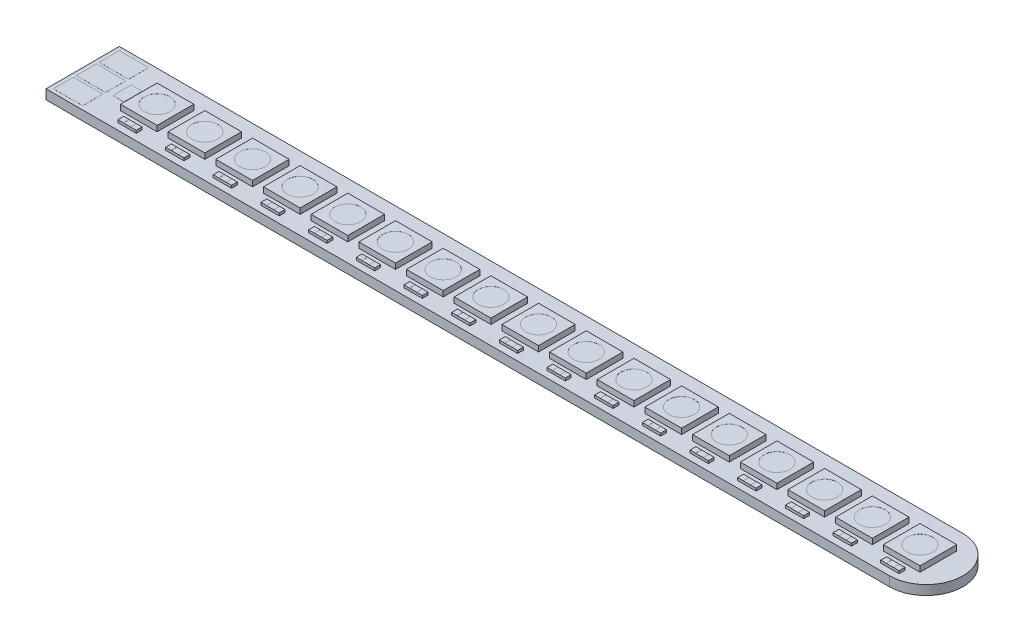
SolidWorks part; units mm, degrees
ref_plane "Front Plane" through (0, 0, 0) normal (0, 0, 1) x (1, 0, 0)
ref_plane "Top Plane" through (0, 0, 0) normal (0, 1, 0) x (1, 0, 0)
ref_plane "Right Plane" through (0, 0, 0) normal (1, 0, 0) x (0, 0, -1)
sketch "Sketch2" plane through (0, 0, 0) normal (0, 1, 0) x (1, 0, 0)
  line L0 (60, 0) -> (-60, 0) construction
  line L3 (55, 5) -> (-60, 5)
  line L4 (-60, 5) -> (-60, -5)
  line L5 (-60, -5) -> (55, -5)
  line L6 (-57.5, 1.75) -> (-57.5, -1.75) construction
  line L7 (-59.5, 4.5) -> (-55.5, 4.5)
  line L8 (-59.5, 4.5) -> (-59.5, 1.75)
  line L9 (-59.5, 1.75) -> (-55.5, 1.75)
  line L10 (-55.5, 4.5) -> (-55.5, 1.75)
  line L11 (-59.5, 1.375) -> (-55.5, 1.375)
  line L12 (-59.5, 1.375) -> (-59.5, -1.375)
  line L13 (-59.5, -1.375) -> (-55.5, -1.375)
  line L14 (-55.5, 1.375) -> (-55.5, -1.375)
  line L15 (-59.5, -1.75) -> (-55.5, -1.75)
  line L16 (-59.5, -1.75) -> (-59.5, -4.5)
  line L17 (-59.5, -4.5) -> (-55.5, -4.5)
  line L18 (-55.5, -1.75) -> (-55.5, -4.5)
  line L19 (-50.35, -3.3) -> (-50.35, -4.1)
  line L20 (-54.64, 1.25) -> (-53.14, 1.25)
  line L21 (-54.64, 1.25) -> (-54.64, -1.25)
  line L22 (-54.64, -1.25) -> (-53.14, -1.25)
  line L23 (-53.14, 1.25) -> (-53.14, -1.25)
  line L24 (-52.35, 2.5) -> (-47.35, 2.5)
  line L25 (-52.35, 2.5) -> (-52.35, -2.5)
  line L26 (-52.35, -2.5) -> (-47.35, -2.5)
  line L27 (-47.35, 2.5) -> (-47.35, -2.5)
  line L28 (-51.1, -3.3) -> (-48.6, -3.3)
  line L29 (-51.1, -3.3) -> (-51.1, -4.1)
  line L30 (-51.1, -4.1) -> (-48.6, -4.1)
  line L31 (-48.6, -3.3) -> (-48.6, -4.1)
  line L32 (-50.35, -4.1) -> (-49.35, -4.1)
  line L33 (-49.35, -4.1) -> (-49.35, -3.3)
  line L34 (-50.35, -3.7) -> (-49.35, -3.7) construction
  arc A2 (55, -5) -> (55, 5) centre (55, 0) ccw
  circle A3 centre (-49.85, 0) radius 1.75
  point P1 (60, 0)
  point P6 (60, 0)
  point P7 (-55.5, 0)
  point P21 (-57.5, 0)
  point P22 (-53.14, 0)
  point P28 (-59.5, 0)
  point P34 (-49.85, 2.5)
  point P35 (-52.35, 0)
  point P37 (-49.85, -3.3)
  point P51 (-49.85, -3.7)
  dimension "D11" = 3.5
  dimension "D1" = 120
  dimension "D2" = 10
  dimension "D3" = 2.75
  dimension "D4" = 0.5
  dimension "D5" = 0.5
  dimension "D6" = 4
  dimension "D7" = 5.36
  dimension "D8" = 2.5
  dimension "D9" = 1.5
  dimension "D10" = 5
  dimension "D12" = 7.65
  dimension "D13" = 0.9
  dimension "D14" = 2.5
  dimension "D15" = 0.8
  dimension "D16" = 1
extrude "PCB" add sketch "Sketch2" along normal mid plane 1.3 contours L5 A2 L3 L4 L28 L31 L30 L29 L24 L27 L26 L25 L20 L23 L22 L21 L15 L18 L17 L16 L11 L14 L13 L12 L7 L10 L9 L8 | L23 L20 L21 L22 | L14 L11 L12 L13 | L18 L15 L16 L17 | L27 L24 L25 L26 A3 | L10 L7 L8 L9 | A3 | L30 L33 L28 L19 | L33 L30 L31 L28 | L29 L30 L19 L28 region at (2.4999, 0, -0.0066) region at (-57.5, 0, -3.125) region at (-57.5, 0, 0) region at (-57.5, 0, 3.125) region at (-49.85, 0, 3.7) region at (-50.725, 0, 3.7) region at (-48.975, 0, 3.7) region at (-53.89, 0, 0) region at (-49.85, 0, -2.4293) region at (-49.85, 0, 0)
extrude "Contacts" add sketch "Sketch2<3>" along normal mid plane 1.31 contours L10 L7 L8 L9 | L14 L11 L12 L13 | L18 L15 L16 L17 region at (-57.5, 0, -3.125) region at (-57.5, 0, 0) region at (-57.5, 0, 3.125)
sketch "Sketch2<3>" plane through (0, 0, 0) normal (0, 1, 0) x (1, 0, 0) same geometry as "Sketch2"
extrude "Dataline Resistor" add sketch "Sketch2<4>" along normal mid plane 1.31 contours L23 L20 L21 L22 region at (-53.89, 0, 0)
sketch "Sketch2<4>" plane through (0, 0, 0) normal (0, 1, 0) x (1, 0, 0) same geometry as "Sketch2"
extrude "Boss-Extrude5" add sketch "Sketch2<5>" along normal mid plane 2.81 contours L27 L24 L25 L26 A3 region at (-49.85, 0, -2.4293)
sketch "Sketch2<5>" plane through (0, 0, 0) normal (0, 1, 0) x (1, 0, 0) same geometry as "Sketch2"
extrude "Boss-Extrude6" add sketch "Sketch2<6>" along normal mid plane 2.8 contours A3
sketch "Sketch2<6>" plane through (0, 0, 0) normal (0, 1, 0) x (1, 0, 0) same geometry as "Sketch2"
extrude "Boss-Extrude7" add sketch "Sketch2<7>" along normal mid plane 2 contours L29 L30 L19 L28 | L33 L30 L31 L28 region at (-50.725, 0, 3.7) region at (-48.975, 0, 3.7)
sketch "Sketch2<7>" plane through (0, 0, 0) normal (0, 1, 0) x (1, 0, 0) same geometry as "Sketch2"
extrude "Boss-Extrude8" add sketch "Sketch2<8>" along normal mid plane 1.99 contours L30 L33 L28 L19 region at (-49.85, 0, 3.7)
sketch "Sketch2<8>" plane through (0, 0, 0) normal (0, 1, 0) x (1, 0, 0) same geometry as "Sketch2"
pattern_linear "LPattern1" count 17 spacing 6.5 along (1, 0, 0) of "Boss-Extrude5", "Boss-Extrude7", "Boss-Extrude8", "Boss-Extrude6"
sketch "Sketch3" plane through (-60, 0, 0) normal (-1, 0, 0) x (0, 0, 1)
  circle A0 centre (0, 0) radius 0.25
extrude "Cut-Extrude3" cut sketch "Sketch3" against normal blind 10
